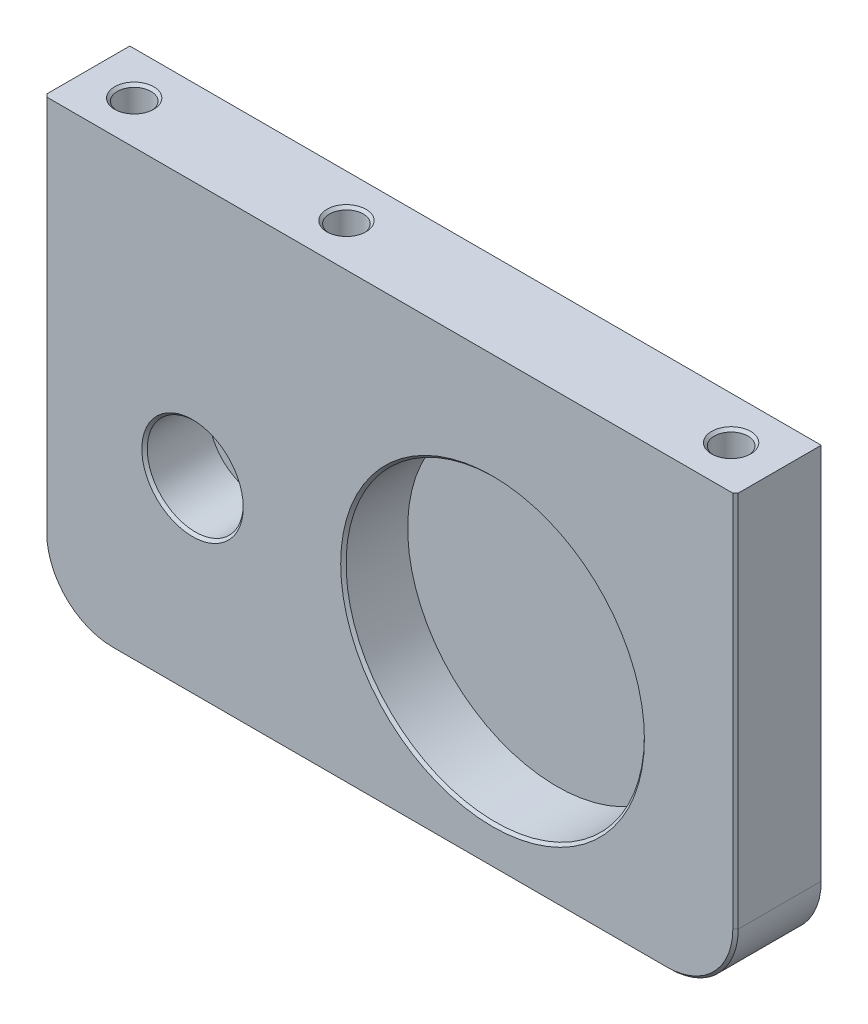
SolidWorks part; units mm, degrees
ref_plane "Front Plane" through (0, 0, 0) normal (0, 0, 1) x (1, 0, 0)
ref_plane "Top Plane" through (0, 0, 0) normal (0, 1, 0) x (1, 0, 0)
ref_plane "Right Plane" through (0, 0, 0) normal (1, 0, 0) x (0, 0, -1)
sketch "Sketch1" plane through (0, 0, 4937.9482) normal (0, 0, 1) x (1, 0, 0)
  line L10 (-33.225, 19.05) -> (18, 19.05)
  line L11 (-33.225, 19.05) -> (-33.225, -14)
  line L12 (-33.225, -14) -> (18, -14)
  line L13 (18, 19.05) -> (18, -14)
  circle A2 centre (0, 0) radius 11.05 construction
  circle A3 centre (-22.225, 0) radius 3.556 construction
  dimension "D2" = 7.112
  dimension "D5" = 19.05
  dimension "D6" = 11
  dimension "D3" = 22.225
  dimension "D1" = 22.1
  dimension "D8" = 51.225
  dimension "D4" = 14
  dimension "D7" = 18
extrude "Boss-Extrude1" add sketch "Sketch1" against normal blind 6.35
sketch "Sketch8" plane through (0, 19.05, 0) normal (0, 1, 0) x (1, 0, 0)
  line L0 (-33.225, -4934.7732) -> (18, -4934.7732) construction
  line L1 (-33.225, -4931.5982) -> (-33.225, -4937.9482) construction
  line L2 (18, -4931.5982) -> (18, -4937.9482) construction
  circle A1 centre (-29.725, -4934.7732) radius 1.25
  circle A2 centre (-14, -4934.7732) radius 1.25
  circle A3 centre (14.5, -4934.7732) radius 1.25
  dimension "D1" = 2.5
  dimension "D2" = 3.5
  dimension "D3" = 3.5
  dimension "D4" = 14
extrude "Cut-Extrude4" cut sketch "Sketch8" against normal blind 15
fillet "Fillet3" radius 5.08 2 edges at (18, -14, 4934.7732) (-33.225, -14, 4934.7732)
sketch "Sketch10" plane through (0, 0, 4937.9482) normal (0, 0, 1) x (1, 0, 0)
  circle A0 centre (-22.225, 0) radius 3.556 construction
  circle A1 centre (0, 0) radius 11.05 construction
  circle A2 centre (-22.225, 0) radius 3.556
  circle A3 centre (0, 0) radius 11.05
extrude "Cut-Extrude5" cut sketch "Sketch10" against normal offset from surface (4.7625 mm away) 1.5875 up to face at (-7.6125, -1.6407, 4931.5982)
chamfer "Chamfer2" distance 0.2 angle 45 10 edges at (18, 5.065, 4937.9482) (-33.225, 5.065, 4937.9482) (-31.7371, -12.5121, 4937.9482) (16.5121, -12.5121, 4937.9482) (-7.6125, -14, 4937.9482) (14.5, 19.05, 4936.0232) (-14, 19.05, 4936.0232) (-29.725, 19.05, 4936.0232) (-18.669, 0, 4937.9482) (11.05, 0, 4937.9482)
